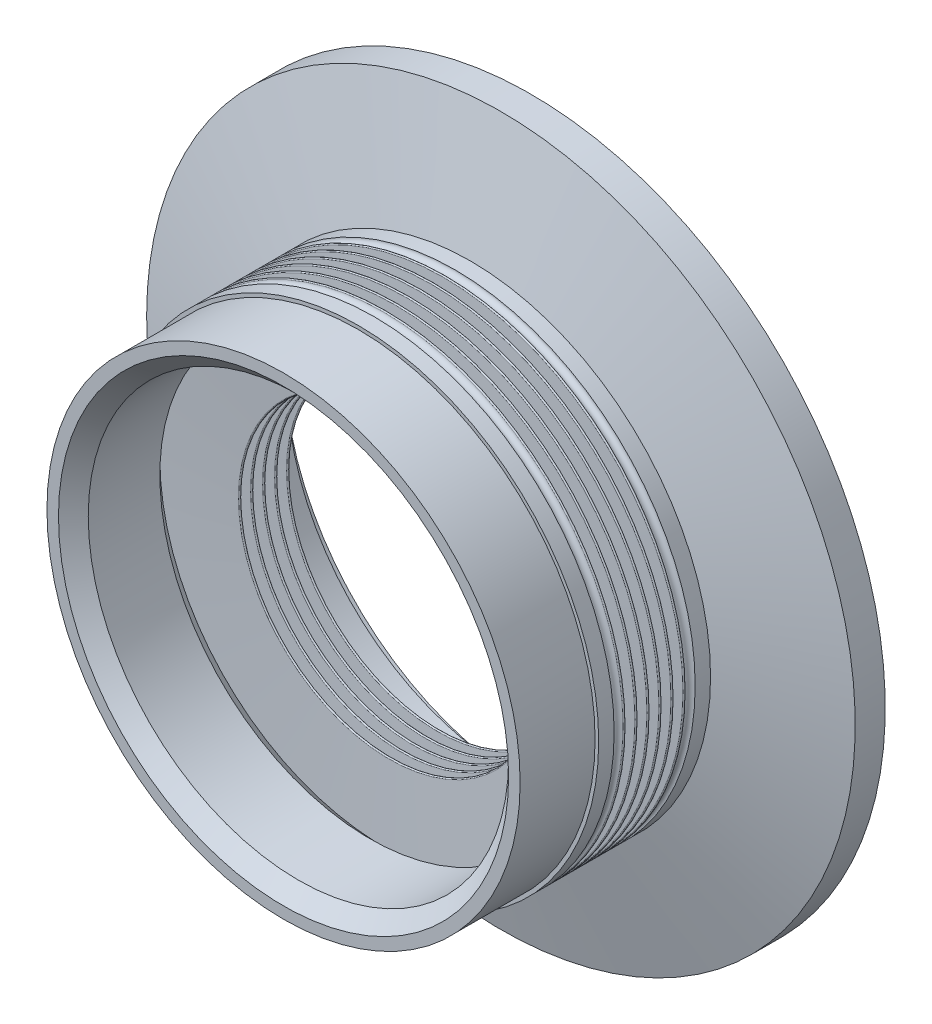
SolidWorks part; units mm, degrees
ref_plane "PL-01 Front" through (0, 0, 0) normal (0, 0, 1) x (1, 0, 0)
ref_plane "PL-02 Top" through (0, 0, 0) normal (0, 1, 0) x (1, 0, 0)
ref_plane "PL-03 Right" through (0, 0, 0) normal (1, 0, 0) x (0, 0, -1)
ref_axis "Axis1" through (0, 0, 7.7945) along (0, 0, 1)
sketch "Sketch2" plane through (0, 0, 0) normal (1, 0, 0) x (0, 0, -1)
  line L0 (0, 25.4) -> (0, 25.2984)
  line L1 (0, 25.2984) -> (-0.5336, 15.9708)
  line L2 (-0.7364, 15.9708) -> (-1.27, 25.2984)
  line L3 (-1.27, 25.2984) -> (-1.27, 25.4)
  line L4 (-0.635, 15.9766) -> (-0.1014, 25.3042)
  line L5 (-0.635, 15.9766) -> (-1.1686, 25.3042)
  line L6 (-7.7057, 0) -> (-23.2855, 0) construction
  line L7 (0, 25.4) -> (-1.27, 25.4) construction
  arc A0 (-0.5336, 15.9708) -> (-0.7364, 15.9708) centre (-0.635, 15.9766) cw
  arc A1 (-0.1014, 25.3042) -> (0, 25.4) centre (0, 25.2984) cw
  arc A2 (-1.1686, 25.3042) -> (-1.27, 25.4) centre (-1.27, 25.2984) ccw
  dimension "D2" = 31.75
  dimension "D1" = 50.8
  dimension "D3" = 1.27
  dimension "D4" = 0.1016
revolve "Revolve1" add sketch "Sketch2" angle 360 about axis through (0, 0, 7.7945) along (0, 0, 1)
pattern_linear "LPattern1" count 5 spacing 1.27 along (0, 0, 1) of "Revolve1"
sketch "Sketch8" plane through (0, 0, 0) normal (1, 0, 0) x (0, 0, -1)
  line L0 (1.1091, 25.4) -> (2.7362, 25.4)
  line L1 (2.7362, 25.4) -> (5.969, 37.465)
  line L2 (5.969, 37.465) -> (9.144, 37.465)
  line L3 (9.144, 37.465) -> (9.144, 26.1112)
  line L4 (9.144, 26.1112) -> (7.112, 26.1112)
  line L5 (7.112, 26.1112) -> (7.112, 23.749)
  line L6 (7.112, 23.749) -> (0.762, 23.749)
  line L7 (0, 24.511) -> (0, 25.4)
  line L9 (10.668, 0) -> (25.2738, 0) construction
  line L10 (0, 24.511) -> (0.762, 23.749)
  arc A0 (0.1002, 25.3153) -> (1.1091, 25.4) centre (0.6011, 25.4) ccw
  arc A1 (0.1002, 25.3153) -> (0, 25.4) centre (0, 25.2984) ccw
  dimension "D1" = 0.1016
  dimension "D2" = 0.508
  dimension "D3" = 15
  dimension "D4" = 9.144
  dimension "D5" = 3.175
  dimension "D6" = 2.032
  dimension "D7" = 52.2224
  dimension "D8" = 1.651
  dimension "D9" = 74.93
  dimension "D10" = 0.762
  dimension "D11" = 45
revolve "Revolve4" add sketch "Sketch8" angle 360 about axis through (0, 0, 7.7945) along (0, 0, 1)
sketch "Sketch9" plane through (0, 0, 0) normal (1, 0, 0) x (0, 0, -1)
  line L0 (-6.35, 23.749) -> (-7.874, 22.225)
  line L1 (-6.35, 23.749) -> (-6.35, 25.4)
  line L2 (-7.4591, 25.4) -> (-9.0932, 25.4)
  line L3 (-9.0932, 25.4) -> (-9.0932, 25.019)
  line L4 (-9.0932, 25.019) -> (-17.018, 25.019)
  line L5 (-17.018, 25.019) -> (-17.018, 22.225)
  line L7 (-34.4132, 0) -> (-26.3828, 0) construction
  line L12 (-7.874, 22.225) -> (-17.018, 22.225)
  arc A0 (-7.4591, 25.4) -> (-6.4502, 25.3153) centre (-6.9511, 25.4) ccw
  arc A1 (0.1002, 25.3153) -> (1.1091, 25.4) centre (0.6011, 25.4) ccw construction
  arc A2 (-6.4502, 25.3153) -> (-6.35, 25.4) centre (-6.35, 25.2984) cw
  arc A3 (0.1002, 25.3153) -> (0, 25.4) centre (0, 25.2984) ccw construction
  dimension "D2" = 3.175
  dimension "D3" = 10.668
  dimension "D4" = 7.9248
  dimension "D5" = 45
  dimension "D6" = 1.524
  dimension "D10" = 50.038
revolve "Revolve5" add sketch "Sketch9" angle 360 about L7
chamfer "Chamfer1" distance 1.5748 angle 45 1 edges at (22.225, 0, 17.018)
